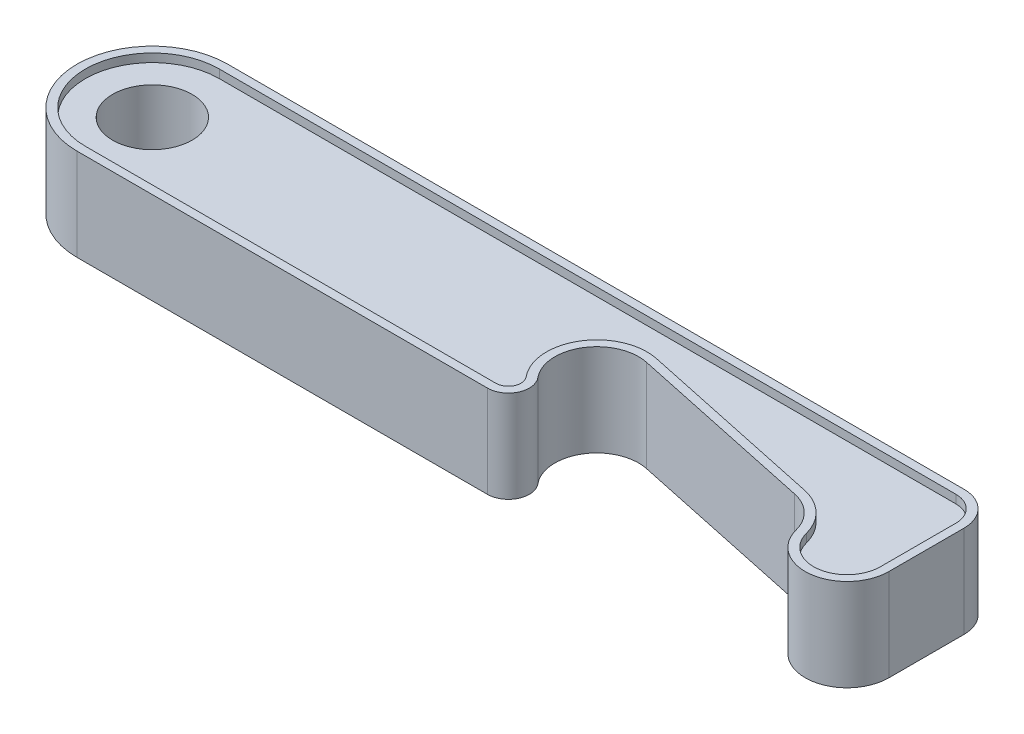
SolidWorks part; units mm, degrees
material "AISI 1020"
ref_plane "Front Plane" through (0, 0, 0) normal (0, 0, 1) x (1, 0, 0)
ref_plane "Top Plane" through (0, 0, 0) normal (0, 1, 0) x (1, 0, 0)
ref_plane "Right Plane" through (0, 0, 0) normal (1, 0, 0) x (0, 0, -1)
sketch "Sketch6" plane through (0, 0, 0) normal (0, 1, 0) x (1, 0, 0)
  line L0 (0, 9) -> (88, 9)
  line L1 (92, 5) -> (92, -4)
  line L2 (78.3571, -1.6093) -> (55.8571, 3.1733)
  line L3 (49.0402, -9) -> (0, -9)
  line L4 (0, 8) -> (88, 8)
  line L5 (91, 5) -> (91, -4)
  line L6 (78.565, -0.6311) -> (56.065, 4.1514)
  line L7 (49.0402, -8) -> (0, -8)
  circle A0 centre (0, 0) radius 4.75
  arc A1 (88, 9) -> (92, 5) centre (88, 5) cw
  arc A2 (92, -4) -> (82.1588, -5.25) centre (87, -4) cw
  arc A3 (82.1588, -5.25) -> (78.3571, -1.6093) centre (77.3175, -6.5) ccw
  arc A4 (55.8571, 3.1733) -> (50.966, -4.9058) centre (54.8175, -1.7175) ccw
  arc A5 (50.966, -4.9058) -> (49.0402, -9) centre (49.0402, -6.5) cw
  arc A6 (0, -9) -> (0, 9) centre (0, 0) cw
  arc A7 (0, -8) -> (0, 8) centre (0, 0) cw
  arc A8 (88, 8) -> (91, 5) centre (88, 5) cw
  arc A9 (91, -4) -> (83.127, -5) centre (87, -4) cw
  arc A10 (83.127, -5) -> (78.565, -0.6311) centre (77.3175, -6.5) ccw
  arc A11 (56.065, 4.1514) -> (50.1957, -5.5435) centre (54.8175, -1.7175) ccw
  arc A12 (50.1957, -5.5435) -> (49.0402, -8) centre (49.0402, -6.5) cw
  point P22 (-9, 0)
  point P37 (0, 0)
  point P38 (0, 0)
  point P39 (0, 0)
  point P40 (0, 0)
  point P41 (0, 0)
  dimension "D1" = 9.5
  dimension "D2" = 9
  dimension "D4" = 4
  dimension "D5" = 2.5
  dimension "D6" = 5
  dimension "D3" = 101
  dimension "D8" = 12
  dimension "D7" = 22.5
  dimension "D9" = 13
  dimension "D10" = 1
extrude "Boss-Extrude1" add sketch "Sketch6" along normal mid plane 9 contours A12 A11 L6 A10 A9 L5 A8 L4 A7 L7 A0 region at (38.4301, 0, -0.8544)
extrude "Boss-Extrude2" add sketch "Sketch6<3>" along normal mid plane 11 contours A6 L3 A5 A4 L2 A3 A2 L1 A1 L0 A11 A12 L7 A7 L4 A8 L5 A9 A10 L6 region at (44, 0, -8.8974)
sketch "Sketch6<3>" plane through (0, 0, 0) normal (0, 1, 0) x (1, 0, 0) same geometry as "Sketch6"
equation "\"A\"= 101mm"
equation "\"B\"= 11mm"
equation "\"C\"= 1mm"
equation "\"D3@Sketch6\"=\"A\""
equation "\"D1@Boss-Extrude2\"=\"B\""
equation "\"D1@Boss-Extrude1\"=\"B\"-(\"C\"*2mm)"
equation "\"D10@Sketch6\"=\"C\""
